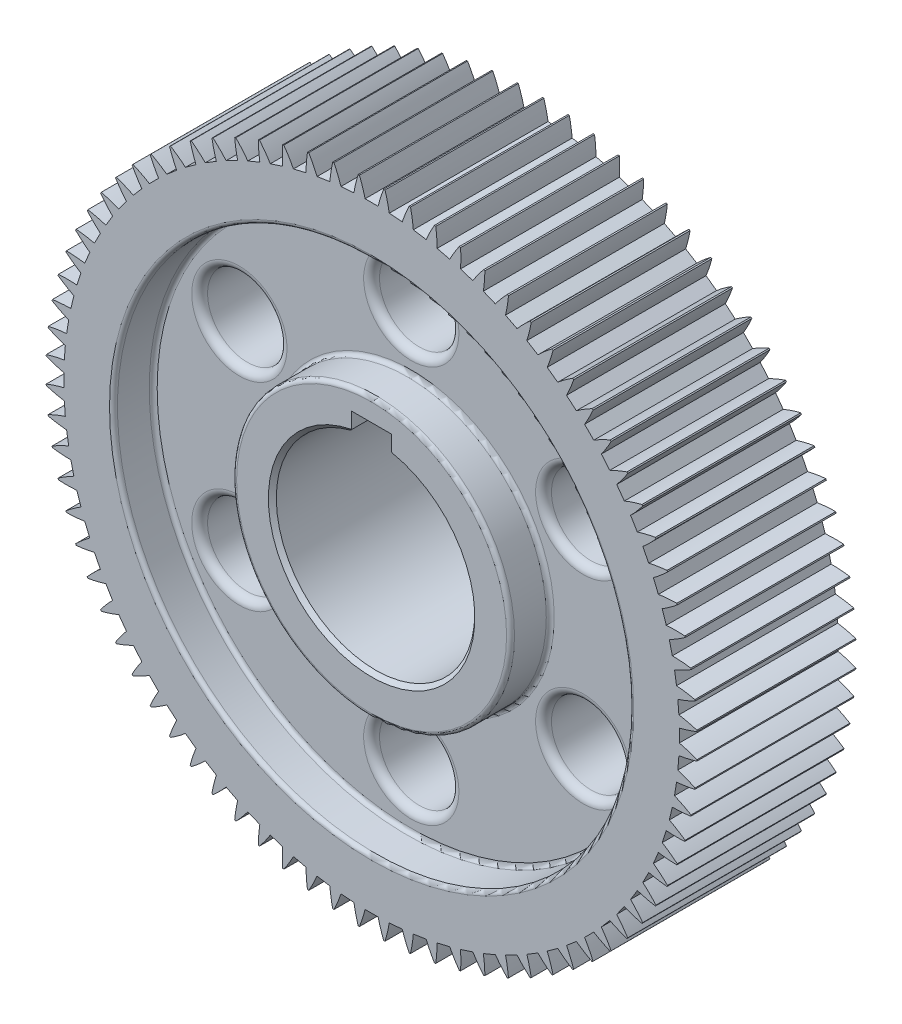
SolidWorks part; units mm, degrees
note: The reader was unsure of these and kept them because the rebuilt part matched: shared geometry of "Sketch5<3>".
ref_plane "Front Plane" through (0, 0, 0) normal (0, 0, 1) x (1, 0, 0)
ref_plane "Top Plane" through (0, 0, 0) normal (0, 1, 0) x (1, 0, 0)
ref_plane "Right Plane" through (0, 0, 0) normal (1, 0, 0) x (0, 0, -1)
sketch "Sketch1" plane through (0, 0, 0) normal (0, 0, 1) x (1, 0, 0)
  circle A0 centre (0, 0) radius 80
  circle A1 centre (0, 0) radius 77.5
  circle A2 centre (0, 0) radius 82
  dimension "D1" = 164
  dimension "D2" = 160
  dimension "D3" = 155
extrude "Boss-Extrude1" add sketch "Sketch1" along normal blind 40 contours A2
sketch "Sketch3" plane through (0, 0, 40) normal (0, 0, 1) x (1, 0, 0)
  line L0 (0, 0) -> (0, -14.5028) construction
  line L1 (0, 0) -> (-0.7798, 39.7073) construction
  line L3 (3.0822, 82) -> (-3.0822, 82)
  line L4 (1.6357, 77.5) -> (-1.6357, 77.5)
  arc A0 (-1.6357, 77.5) -> (-3.0822, 82) centre (-34.379, 69.4574) ccw
  circle A1 centre (0, 0) radius 82 construction
  arc A2 (1.6357, 77.5) -> (3.0822, 82) centre (34.379, 69.4574) cw
  circle A5 centre (0, 0) radius 77.5 construction
  point P8 (0, 82)
  point P12 (0, 77.5)
  dimension "D1" = 1.125
extrude "Cut-Extrude1" cut sketch "Sketch3" against normal through all
pattern_circular "CirPattern1" count 80 over 360 about axis through (0, 0, 0) along (0, 0, 1) of "Cut-Extrude1"
sketch "Sketch4" plane through (0, 0, 40) normal (0, 0, 1) x (1, 0, 0)
  line L6 (-5, 24.4949) -> (-5, 29.4949)
  line L7 (-5, 29.4949) -> (5, 29.4949)
  line L8 (5, 24.4949) -> (5, 29.4949)
  arc A0 (-5, 24.4949) -> (5, 24.4949) centre (0, 0) ccw
  dimension "D1" = 50
  dimension "D2" = 5
  dimension "D3" = 10
  dimension "D4" = 5
extrude "Cut-Extrude2" cut sketch "Sketch4" against normal through all
sketch "Sketch5" plane through (0, 0, 40) normal (0, 0, 1) x (1, 0, 0)
  circle A0 centre (0, 0) radius 35
  circle A1 centre (0, 0) radius 65
  dimension "D1" = 70
  dimension "D2" = 130
extrude "Cut-Extrude3" cut sketch "Sketch5" against normal blind 10 contours A0 | A1
extrude "Cut-Extrude5" cut sketch "Sketch5<3>" against normal blind 10 from offset 30 offset against normal yes
sketch "Sketch5<3>" plane through (0, 0, 40) normal (0, 0, 1) x (1, 0, 0) same geometry as "Sketch5"
sketch "Sketch6" plane through (0, 0, 30) normal (0, 0, 1) x (1, 0, 0)
  circle A0 centre (0, 50) radius 10
  dimension "D1" = 50
  dimension "D2" = 20
extrude "Cut-Extrude6" cut sketch "Sketch6" against normal through all
pattern_circular "CirPattern2" count 6 over 360 about axis through (0, 0, 0) along (0, 0, 1) of "Cut-Extrude6"
chamfer "Chamfer1" distance 1 angle 45 4 edges at (-5, 24.4949, 20) (0, -25, 0) (5, 24.4949, 20) (0, -25, 40)
fillet "Fillet1" radius 1 4 edges at (35, 0, 10) (35, 0, 0) (35, 0, 40) (35, 0, 30)
fillet "Fillet2" radius 1 4 edges at (65, 0, 40) (65, 0, 30) (65, 0, 10) (65, 0, 0)
fillet "Fillet3" radius 2 12 edges at (-33.3013, -25, 10) (-48.3013, -16.3397, 30) (10, -50, 10) (-10, -50, 30) (53.3013, -25, 10) (38.3013, -33.6603, 30) (53.3013, 25, 10) (48.3013, 16.3397, 30) (10, 50, 10) (10, 50, 30) (-33.3013, 25, 10) (-38.3013, 33.6603, 30)
equation "\"module\"= 2"
equation "\"teeth\"= 80"
equation "\"D1@Sketch1\"=\"module\"*(\"teeth\"+2)"
equation "\"D2@Sketch1\"=\"module\"*\"teeth\""
equation "\"D3@Sketch1\"=\"module\"*(\"teeth\"-2.5)"
equation "\"D1@Sketch3\"=360/(\"teeth\"*4)"
equation "\"D1@CirPattern1\"=\"teeth\""
